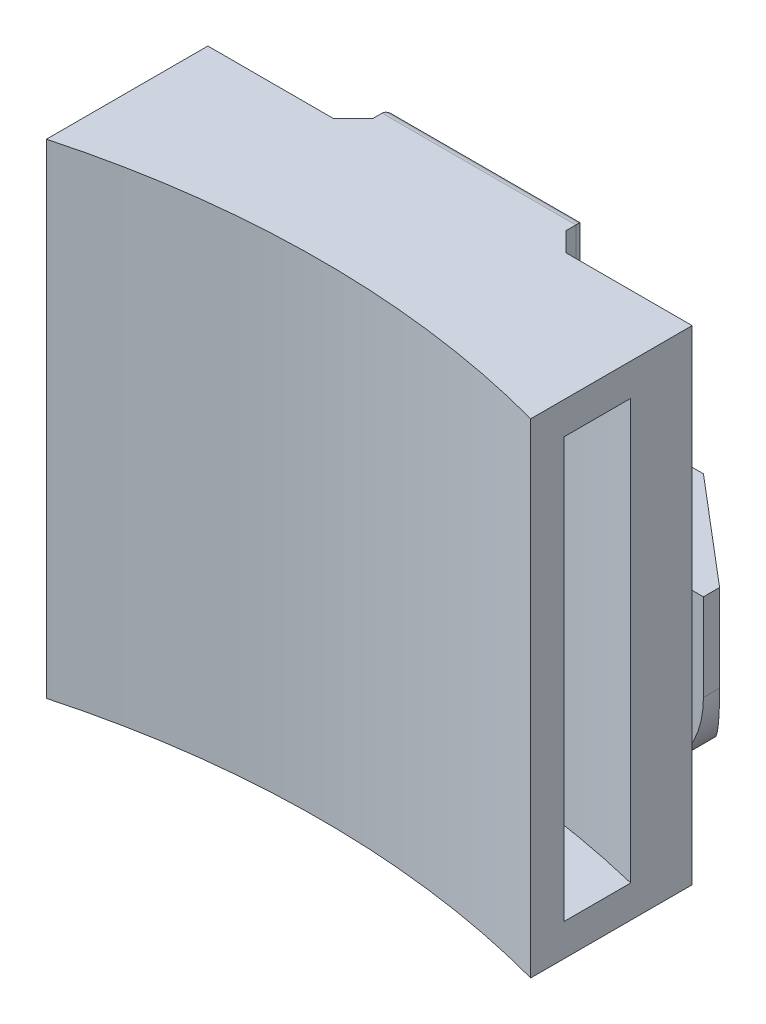
SolidWorks part; units mm, degrees
ref_plane "Front Plane" through (0, 0, 0) normal (0, 0, 1) x (1, 0, 0)
ref_plane "Top Plane" through (0, 0, 0) normal (0, 1, 0) x (1, 0, 0)
ref_plane "Right Plane" through (0, 0, 0) normal (1, 0, 0) x (0, 0, -1)
sketch "Sketch1" plane through (0, 0, 0) normal (0, 1, 0) x (1, 0, 0)
  line L0 (-2.35, 5.5) -> (2.35, 5.5)
  line L1 (2.35, 5.5) -> (5.65, 2.7)
  line L2 (5.65, 2.7) -> (5.65, 2.2)
  line L3 (5.65, 2.2) -> (2.5, 2.2)
  line L4 (2.5, 2.2) -> (2.5, 0)
  line L5 (2.5, 0) -> (7.5, 0)
  line L6 (7.5, 0) -> (7.5, -5)
  line L7 (0, -55) -> (0, 55) construction
  line L8 (-7.5, 0) -> (-7.5, -5)
  line L9 (-2.5, 0) -> (-7.5, 0)
  line L10 (-2.5, 2.2) -> (-2.5, 0)
  line L11 (-5.65, 2.2) -> (-2.5, 2.2)
  line L12 (-5.65, 2.7) -> (-5.65, 2.2)
  line L13 (-2.35, 5.5) -> (-5.65, 2.7)
  arc A0 (7.5, -5) -> (-7.5, -5) centre (0, -32.625) ccw
  dimension "D1" = 2.2
  dimension "D2" = 4.7
  dimension "D3" = 5.5
  dimension "D4" = 11.3
  dimension "D5" = 0.5
  dimension "D6" = 5
  dimension "D7" = 15
  dimension "D8" = 4
  dimension "D9" = 5
extrude "Boss-Extrude1" add sketch "Sketch1" along normal mid plane 15
sketch "Sketch2" plane through (0, 7.5, 0) normal (0, 1, 0) x (1, 0, 0)
  line L0 (-2.5, 0) -> (2.5, 0)
  line L13 (-2.35, 5.5) -> (-5.65, 2.7)
  line L14 (-5.65, 2.7) -> (-5.65, 2.2)
  line L15 (-5.65, 2.2) -> (-2.5, 2.2)
  line L16 (-2.5, 2.2) -> (-2.5, 0)
  line L17 (-2.5, 0) -> (-7.5, 0)
  line L18 (-7.5, 0) -> (-7.5, -5)
  line L19 (7.5, -5) -> (7.5, 0)
  line L20 (7.5, 0) -> (2.5, 0)
  line L21 (2.5, 0) -> (2.5, 2.2)
  line L22 (2.5, 2.2) -> (5.65, 2.2)
  line L23 (5.65, 2.2) -> (5.65, 2.7)
  line L24 (5.65, 2.7) -> (2.35, 5.5)
  line L25 (2.35, 5.5) -> (-2.35, 5.5)
  line L26 (-2.35, 5.5) -> (-5.65, 2.7)
  line L27 (-5.65, 2.7) -> (-5.65, 2.2)
  line L28 (-5.65, 2.2) -> (-2.5, 2.2)
  line L29 (-2.5, 2.2) -> (-2.5, 0)
  line L34 (2.5, 0) -> (2.5, 2.2)
  line L35 (2.5, 2.2) -> (5.65, 2.2)
  line L36 (5.65, 2.2) -> (5.65, 2.7)
  line L37 (5.65, 2.7) -> (2.35, 5.5)
  line L38 (2.35, 5.5) -> (-2.35, 5.5)
  arc A1 (7.5, -5) -> (-7.5, -5) centre (0, -32.625) ccw
  dimension "D1" = 0
extrude "Cut-Extrude2" cut sketch "Sketch2" against normal offset from surface (9.3 mm away) 5.7 up to face at (0, -7.5, -1.1571)
fillet "Fillet1" radius 3 4 edges at (5.65, -7.5, -2.45) (2.5, -7.5, -1.1) (-2.5, -1.8, -1.1) (-5.65, -1.8, -2.45)
fillet "Fillet2" radius 0.7 9 edges at (2.5, -3.15, -2.2) (2.5, -3.15, 0) (-2.5, -6.15, -2.2) (-2.5, -6.15, 0) (1.5, -1.8, 0) (-1.6213, -2.6787, -2.2) (-1.6213, -2.6787, 0) (1.6213, -6.6213, -2.2) (1.6213, -6.6213, 0)
sketch "Sketch3" plane through (0, 0, 0) normal (0, 0, -1) x (-1, 0, 0)
  line L0 (-7.5, 7.5) -> (7.5, 7.5) construction
  line L1 (3, 3.5) -> (-3, 3.5)
  line L2 (3, 3.5) -> (3, 7.5)
  line L3 (3, 7.5) -> (-3, 7.5)
  line L4 (-3, 3.5) -> (-3, 7.5)
  line L5 (3, 3.5) -> (-3, 7.5) construction
  line L6 (3, 7.5) -> (-3, 3.5) construction
  point P0 (0, 5.5)
  dimension "D1" = 4
  dimension "D2" = 6
extrude "Boss-Extrude2" add sketch "Sketch3" along normal blind 1.2
sketch "Sketch5" plane through (0, 0, 0) normal (0, 0, -1) x (-1, 0, 0)
  line L0 (0, 5.775) -> (0, -5.775) construction
  line L1 (3, 7.5) -> (7.5, 7.5) construction
  circle A0 centre (6, 5.5) radius 0.75
  circle A1 centre (-6, 5.5) radius 0.75
  dimension "D1" = 1.5
  dimension "D2" = 12
  dimension "D3" = 2
extrude "Boss-Extrude3" add sketch "Sketch5" along normal blind 0.6 draft 35
sketch "Sketch6" plane through (0, 0, 0) normal (0, 1, 0) x (1, 0, 0)
  line L4 (-7.5, 0) -> (-7.5, -5) construction
  line L5 (-7.5, -1.9022) -> (-7.5, -3.9651)
  line L6 (7.5, -5) -> (7.5, 0) construction
  line L7 (7.5, -3.9651) -> (7.5, -1.9022)
  arc A0 (7.762, -4.0349) -> (-7.762, -4.0349) centre (0, -32.625) ccw construction
  arc A1 (7.5, -5) -> (-7.5, -5) centre (0, -32.625) ccw construction
  arc A2 (7.5, -5) -> (-7.5, -5) centre (0, -32.625) ccw construction
  arc A3 (7.5, -3.9651) -> (-7.5, -3.9651) centre (0, -32.625) ccw
  arc A4 (7.5, -1.9022) -> (-7.5, -1.9022) centre (0, -32.625) ccw
  arc A5 (8.286, -2.1048) -> (-8.286, -2.1048) centre (0, -32.625) ccw construction
  dimension "D1" = 1
  dimension "D2" = 2
extrude "Cut-Extrude3" cut sketch "Sketch6" against normal mid plane 13
chamfer "Chamfer1" distance 0.6 angle 45 2 edges at (3, 5.5, 0) (-3, 5.5, 0)
fillet "Fillet3" radius 0.3 4 edges at (0, 7.5, -1.2) (-3, 5.5, -1.2) (0, 3.5, -1.2) (3, 5.5, -1.2)
